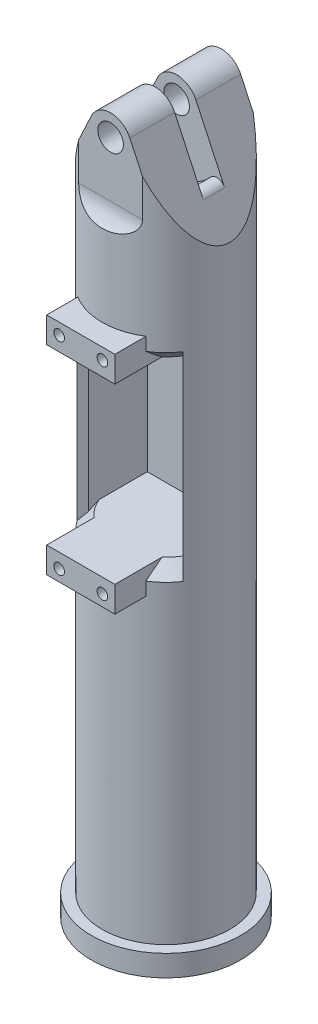
SolidWorks part; units mm, degrees
ref_plane "Front Plane" through (0, 0, 0) normal (0, 0, 1) x (1, 0, 0)
ref_plane "Top Plane" through (0, 0, 0) normal (0, 1, 0) x (1, 0, 0)
ref_plane "Right Plane" through (0, 0, 0) normal (1, 0, 0) x (0, 0, -1)
sketch "Sketch1" plane through (0, 0, 0) normal (0, 1, 0) x (1, 0, 0)
  circle A0 centre (0, 0) radius 15
  dimension "D1" = 30
extrude "Boss-Extrude1" add sketch "Sketch1" along normal blind 170
sketch "Sketch2" plane through (0, 0, 0) normal (0, 0, 1) x (1, 0, 0)
  line L0 (-10.5, 160) -> (-10.5, 182.2206)
  line L1 (-10.5, 182.2206) -> (10.5, 182.2206)
  line L2 (10.5, 182.2206) -> (10.5, 160)
  line L3 (15, 170) -> (-15, 170) construction
  arc A0 (-10.5, 160) -> (10.5, 160) centre (0, 160) ccw
  dimension "D1" = 21
  dimension "D2" = 10
extrude "Cut-Extrude1" cut sketch "Sketch2" against normal mid plane 5
sketch "Sketch3" plane through (0, 0, 0) normal (1, 0, 0) x (0, 0, -1)
  line L0 (-15, 170) -> (-13, 170)
  line L1 (15, 170) -> (-15, 170) construction
  line L2 (-13, 170) -> (-13, 152)
  line L3 (-15, 170) -> (-15, 147.5279)
  line L4 (-15, 170) -> (-15, 0) construction
  line L5 (0, 170) -> (0, 145.7961) construction
  line L6 (15, 170) -> (15, 147.5279)
  line L7 (13, 170) -> (13, 152)
  line L8 (15, 170) -> (13, 170)
  arc A0 (-15, 147.5279) -> (-13, 152) centre (-19, 152) ccw
  arc A1 (15, 147.5279) -> (13, 152) centre (19, 152) cw
  dimension "D1" = 12
  dimension "D2" = 18
  dimension "D3" = 2
extrude "Cut-Extrude2" cut sketch "Sketch3" against normal through all both and the other way through all
sketch "Sketch4" plane through (0, 0, 13) normal (0, 0, 1) x (1, 0, 0)
  line L0 (7.4833, 170) -> (-7.4833, 170) construction
  circle A0 centre (0, 165) radius 3
  dimension "D1" = 6
  dimension "D2" = 5
extrude "Cut-Extrude3" cut sketch "Sketch4" against normal through all
sketch "Sketch5" plane through (0, 0, 13) normal (0, 0, 1) x (1, 0, 0)
  line L0 (-4.5315, 167.1131) -> (-15, 144.6634)
  line L1 (-15, 144.6634) -> (-15, 175.2765)
  line L2 (-15, 175.2765) -> (15, 175.2765)
  line L3 (15, 175.2765) -> (15, 144.6634)
  line L4 (15, 144.6634) -> (4.5315, 167.1131)
  line L5 (0, 165) -> (0, 175.2765) construction
  line L6 (7.4833, 170) -> (-7.4833, 170) construction
  arc A0 (4.5315, 167.1131) -> (-4.5315, 167.1131) centre (0, 165) ccw
  dimension "D1" = 50
  dimension "D2" = 30
extrude "Cut-Extrude4" cut sketch "Sketch5" against normal through all
fillet "Fillet1" radius 2 2 edges at (-9.7108, 156.0062, 0) (9.7108, 156.0062, 0)
sketch "Sketch6" plane through (0, 0, 0) normal (0, 0, 1) x (1, 0, 0)
  line L0 (0, 0) -> (0, 102) construction
  line L1 (-8, 75.585) -> (8, 75.585)
  line L2 (-8, 75.585) -> (-8, 128.415)
  line L3 (-8, 128.415) -> (8, 128.415)
  line L4 (8, 75.585) -> (8, 128.415)
  line L5 (-8, 75.585) -> (8, 128.415) construction
  line L6 (-8, 128.415) -> (8, 75.585) construction
  point P0 (0, 102)
  dimension "D1" = 52.83
  dimension "D2" = 16
  dimension "D3" = 102
extrude "Boss-Extrude2" add sketch "Sketch6" along normal blind 20
sketch "Sketch7" plane through (0, 0, 20) normal (0, 0, 1) x (1, 0, 0)
  line L0 (0, 128.415) -> (0, 75.585) construction
  line L1 (8, 128.415) -> (-8, 128.415) construction
  line L2 (-8, 75.585) -> (8, 75.585) construction
  line L4 (-11.0853, 122.35) -> (11.0853, 122.35)
  line L5 (-11.0853, 122.35) -> (-11.0853, 81.65)
  line L6 (-11.0853, 81.65) -> (11.0853, 81.65)
  line L7 (11.0853, 122.35) -> (11.0853, 81.65)
  line L8 (-11.0853, 122.35) -> (11.0853, 81.65) construction
  line L9 (-11.0853, 81.65) -> (11.0853, 122.35) construction
  point P6 (0, 102)
  dimension "D1" = 40.7
extrude "Cut-Extrude5" cut sketch "Sketch7" against normal blind 26.7
sketch "Sketch8" plane through (0, 0, 20) normal (0, 0, 1) x (1, 0, 0)
  line L0 (-5.08, 125.749) -> (-5.08, 78.251) construction
  line L3 (-5.08, 125.749) -> (-8, 125.749) construction
  line L4 (-8, 128.415) -> (-8, 122.35) construction
  line L5 (5.08, 125.749) -> (8, 125.749) construction
  line L6 (8, 122.35) -> (8, 128.415) construction
  line L7 (-5.08, 125.749) -> (-5.08, 128.415) construction
  line L8 (8, 128.415) -> (-8, 128.415) construction
  line L9 (-5.08, 78.251) -> (-5.08, 75.585) construction
  line L10 (-8, 75.585) -> (8, 75.585) construction
  circle A0 centre (-5.08, 125.749) radius 1.25
  circle A1 centre (-5.08, 78.251) radius 1.25
  circle A2 centre (5.08, 125.749) radius 1.25
  circle A3 centre (5.08, 78.251) radius 1.25
  point P6 (0, 0)
  point P21 (0, 0)
  dimension "D1" = 47.498
  dimension "D2" = 2.5
  dimension "D4" = 10.16
extrude "Cut-Extrude6" cut sketch "Sketch8" against normal blind 6
sketch "Sketch9" plane through (0, 0, 0) normal (0, -1, 0) x (1, 0, 0)
  circle A0 centre (0, 0) radius 17.5
  dimension "D1" = 35
extrude "Boss-Extrude3" add sketch "Sketch9" against normal blind 5
sketch "Sketch10" plane through (0, 5, 0) normal (0, 1, 0) x (1, 0, 0)
  line L0 (0, 0) -> (0, 13) construction
  circle A0 centre (0, 13) radius 1.5
  circle A1 centre (13, 0) radius 1.5
  circle A2 centre (0, -13) radius 1.5
  circle A3 centre (-13, 0) radius 1.5
  point P13 (0, 0)
  dimension "D1" = 3
  dimension "D2" = 13
  dimension "D3" = 4
extrude "Cut-Extrude7" cut sketch "Sketch10" against normal through all
chamfer "Chamfer1" distance 3 angle 45 6 edges at (-9.6297, 122.35, 11.5009) (9.6297, 122.35, 11.5009) (11.0853, 102, 10.1053) (9.6297, 81.65, 11.5009) (-9.6297, 81.65, 11.5009) (-11.0853, 102, 10.1053) first distance on face at (0, 122.35, 9.0494) first distance on face at (11.0853, 102, 1.7026) first distance on face at (0, 81.65, 9.0494) first distance on face at (-11.0853, 102, 1.7026)
